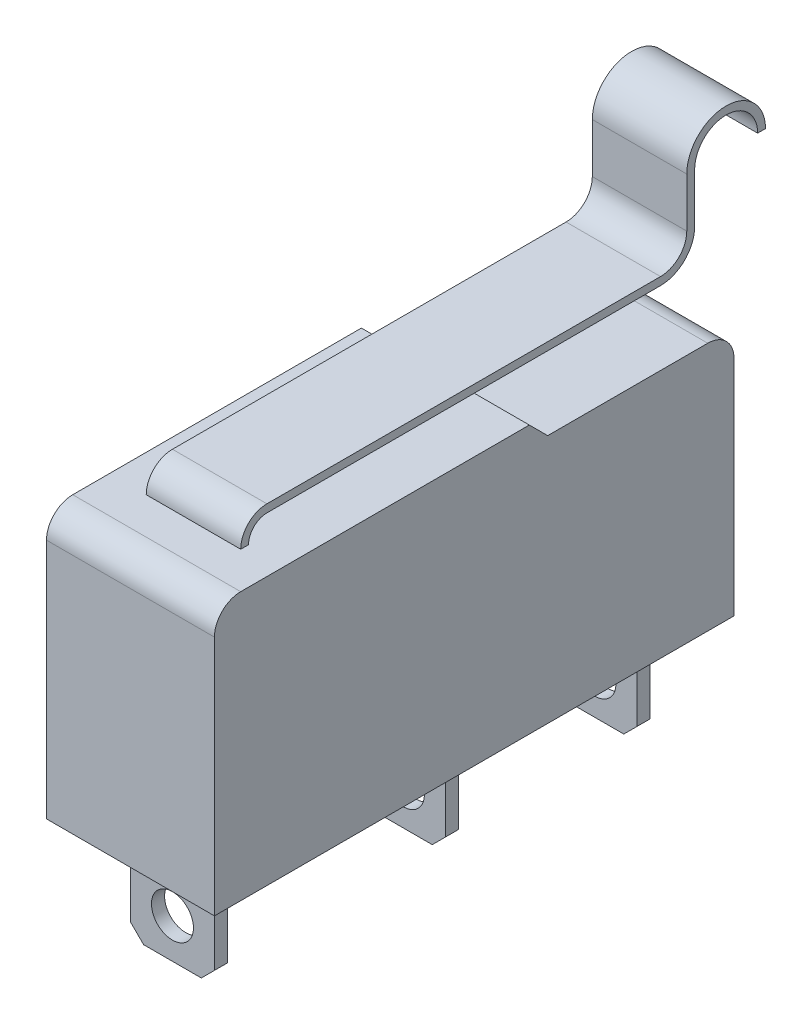
SolidWorks part; units mm, degrees
ref_plane "正面" through (0, 0, 0) normal (0, 0, 1) x (1, 0, 0)
ref_plane "平面" through (0, 0, 0) normal (0, 1, 0) x (1, 0, 0)
ref_plane "右側面" through (0, 0, 0) normal (1, 0, 0) x (0, 0, -1)
sketch "ｽｹｯﾁ1" plane through (0, 0, 0) normal (1, 0, 0) x (0, 0, -1)
  line L0 (12, 10.2) -> (12.7, 9.5)
  line L1 (0, 0) -> (19.8, 0)
  line L2 (0, 0) -> (0, 9.2)
  line L3 (12.7, 9.5) -> (18.8, 9.5)
  line L4 (19.8, 0) -> (19.8, 8.5)
  line L7 (1, 10.2) -> (12, 10.2)
  arc A0 (18.8, 9.5) -> (19.8, 8.5) centre (18.8, 8.5) cw
  arc A1 (0, 9.2) -> (1, 10.2) centre (1, 9.2) cw
  point P7 (19.8, 9.5)
  point P10 (0, 0)
  point P11 (0, 10.1014)
  dimension "D3" = 1
  dimension "D5" = 1
  dimension "D1" = 19.8
  dimension "D2" = 9.5
  dimension "D4" = 10.2
  dimension "D6" = 12
  dimension "D7" = 135
extrude "ﾎﾞｽ - 押し出し1" add sketch "ｽｹｯﾁ1" along normal mid plane 6.4
sketch "ｽｹｯﾁ2" plane through (0, 0, 0) normal (1, 0, 0) x (0, 0, -1)
  line L0 (12, 10.2) -> (1, 10.2) construction
  line L1 (3.4, 11.2) -> (18.4, 11.2)
  line L2 (19.4, 12.2) -> (19.4, 14.0822)
  line L3 (3.4, 10.9) -> (18.4, 10.9)
  line L4 (19.7, 12.2) -> (19.7, 14.0822)
  line L5 (2.4, 10.2) -> (2.7, 10.2)
  line L6 (22.1, 14.0822) -> (22.4, 14.0822)
  line L7 (0, 9.2) -> (0, 0) construction
  line L9 (0, 0) -> (19.8, 0) construction
  arc A0 (2.4, 10.2) -> (3.4, 11.2) centre (3.4, 10.2) cw
  arc A1 (19.4, 14.0822) -> (22.4, 14.0822) centre (20.9, 14.0822) cw
  arc A2 (18.4, 11.2) -> (19.4, 12.2) centre (18.4, 12.2) ccw
  arc A3 (2.7, 10.2) -> (3.4, 10.9) centre (3.4, 10.2) cw
  arc A4 (18.4, 10.9) -> (19.7, 12.2) centre (18.4, 12.2) ccw
  arc A5 (19.7, 14.0822) -> (22.1, 14.0822) centre (20.9, 14.0822) cw
  arc A6 (19.4, 14.0822) -> (22.4, 14.0822) centre (20.9, 14.0822) cw construction
  point P22 (20.9, 15.5822)
  point P25 (20.9, 14.3911)
  dimension "D1" = 1
  dimension "D5" = 1
  dimension "D6" = 1.5
  dimension "D3" = 20.9
  dimension "D4" = 15.5822
  dimension "D7" = 15
  dimension "D2" = 0.3
extrude "ﾎﾞｽ - 押し出し2" add sketch "ｽｹｯﾁ2" along normal mid plane 3.6
sketch "ｽｹｯﾁ3" plane through (0, 0, 0) normal (1, 0, 0) x (0, 0, -1)
  line L0 (0, 0) -> (19.8, 0) construction
  line L1 (1.6, 0) -> (2.1, 0)
  line L2 (1.6, 0) -> (1.6, -3.9)
  line L3 (1.6, -3.9) -> (2.1, -3.9)
  line L4 (2.1, 0) -> (2.1, -3.9)
  line L5 (0, 9.2) -> (0, 0) construction
  line L6 (10.4, 0) -> (10.9, 0)
  line L7 (10.4, 0) -> (10.4, -3.9)
  line L8 (10.4, -3.9) -> (10.9, -3.9)
  line L9 (10.9, 0) -> (10.9, -3.9)
  line L10 (17.7, 0) -> (18.2, 0)
  line L11 (17.7, 0) -> (17.7, -3.9)
  line L12 (17.7, -3.9) -> (18.2, -3.9)
  line L13 (18.2, 0) -> (18.2, -3.9)
  dimension "D1" = 0.5
  dimension "D2" = 3.9
  dimension "D3" = 1.6
  dimension "D4" = 8.8
  dimension "D5" = 7.3
extrude "ﾎﾞｽ - 押し出し3" add sketch "ｽｹｯﾁ3" along normal mid plane 3.2
chamfer "面取り1" distance 0.5 angle 45 6 edges at (-1.6, -3.9, -17.95) (-1.6, -3.9, -10.65) (-1.6, -3.9, -1.85) (1.6, -3.9, -17.95) (1.6, -3.9, -10.65) (1.6, -3.9, -1.85)
sketch "ｽｹｯﾁ4" plane through (0, 0, -18.2) normal (0, 0, -1) x (-1, 0, 0)
  line L0 (0, 0) -> (0, -3.9) construction
  line L1 (-1.1, -3.9) -> (1.1, -3.9) construction
  circle A0 centre (0, -2.4) radius 0.8
  dimension "D1" = 1.6
  dimension "D2" = 1.5
extrude "ｶｯﾄ - 押し出し1" cut sketch "ｽｹｯﾁ4" against normal through all
